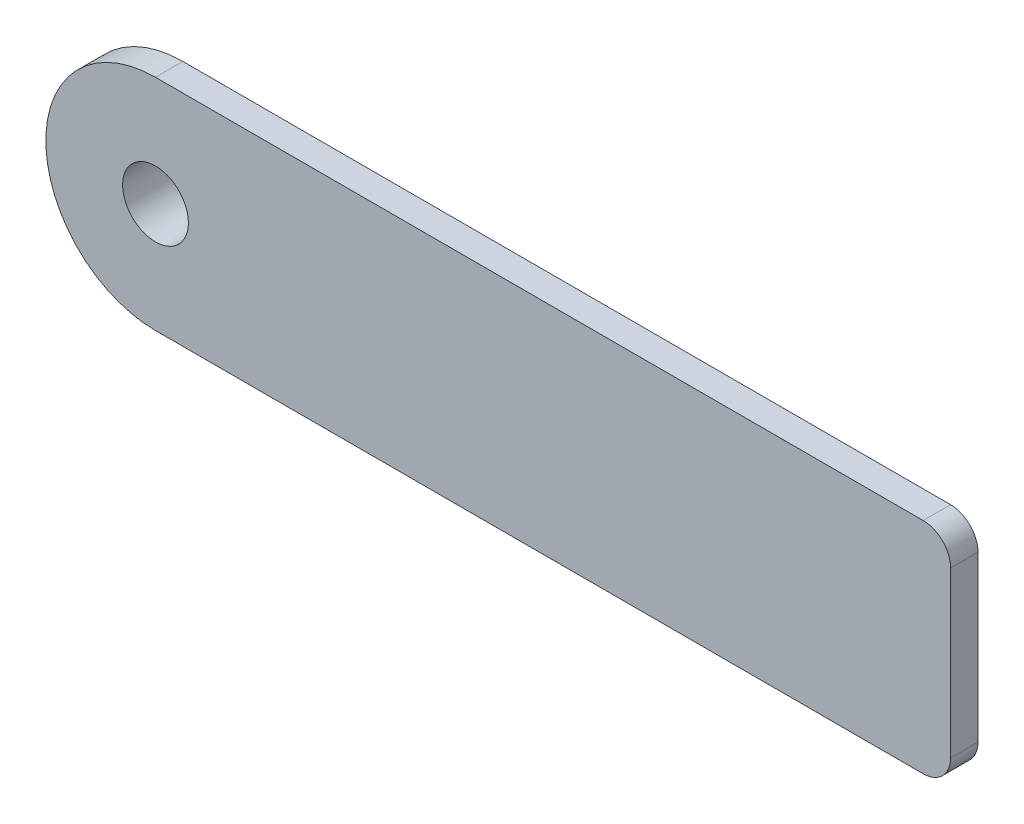
SolidWorks part; units mm, degrees
material "PEI"
ref_plane "Front Plane" through (0, 0, 0) normal (0, 0, 1) x (1, 0, 0)
ref_plane "Top Plane" through (0, 0, 0) normal (0, 1, 0) x (1, 0, 0)
ref_plane "Right Plane" through (0, 0, 0) normal (1, 0, 0) x (0, 0, -1)
sketch "Sketch2" plane through (0, 0, 0) normal (0, 0, 1) x (1, 0, 0)
  line L0 (0, 20) -> (0, -20)
  line L1 (0, 20) -> (145, 20)
  line L2 (0, -20) -> (145, -20)
  line L3 (145, 20) -> (145, -20)
  line L4 (0, 0) -> (-20, 0)
  circle A0 centre (0, 0) radius 20
  circle A1 centre (0, 0) radius 6
  dimension "D1" = 40
  dimension "D3" = 12
  dimension "D2" = 165
extrude "Boss-Extrude1" add sketch "Sketch2" along normal mid plane 5 contours A1 L0 A0 | A0 L2 L3 L1 | A1 L4 A0 L0 | A1 L0 A0 L4 region at (9.0759, 0, 0) region at (80.2769, 0, 0) region at (-9.0759, 9.0759, 0) region at (-9.0759, -9.0759, 0)
fillet "Fillet1" radius 5 2 edges at (145, -20, 0) (145, 20, 0)
sketch "Sketch3" plane through (0, 0, -2.5) normal (0, 0, -1) x (-1, 0, 0)
  line L3 (-145, 15) -> (-145, -15)
  line L4 (-140, -20) -> (0, -20)
  line L5 (0, 20) -> (-140, 20)
  line L6 (-145, 15) -> (-145, -15)
  line L7 (-140, -20) -> (0, -20)
  line L8 (0, 20) -> (-140, 20)
  circle A0 centre (0, 0) radius 12
  arc A3 (-145, -15) -> (-140, -20) centre (-140, -15) ccw
  arc A4 (0, -20) -> (0, 20) centre (0, 0) ccw
  arc A5 (-140, 20) -> (-145, 15) centre (-140, 15) ccw
  arc A6 (-145, -15) -> (-140, -20) centre (-140, -15) ccw
  arc A7 (0, -20) -> (0, 20) centre (0, 0) ccw
  arc A8 (-140, 20) -> (-145, 15) centre (-140, 15) ccw
  circle M13 centre (0, 0) radius 6
  dimension "D2" = 24
  dimension "D1" = 0
extrude "Boss-Extrude2" add sketch "Sketch3" along normal blind 5 contours A0 M13 region at (11.6606, 0, -2.5)
